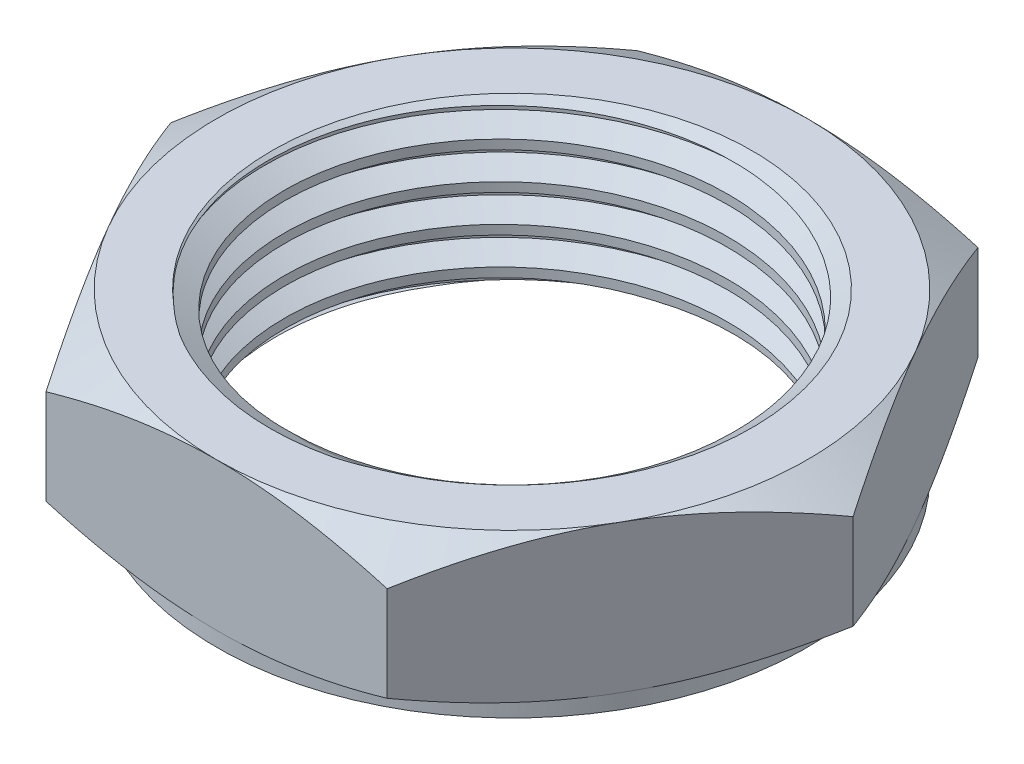
SolidWorks part; units mm, degrees
material "AISI Type 316L stainless steel"
ref_plane "Front Plane" through (0, 0, 0) normal (0, 0, 1) x (1, 0, 0)
ref_plane "Top Plane" through (0, 0, 0) normal (0, 1, 0) x (1, 0, 0)
ref_plane "Right Plane" through (0, 0, 0) normal (1, 0, 0) x (0, 0, -1)
sketch "Sketch1" plane through (0, 0, 0) normal (0, 1, 0) x (1, 0, 0)
  line L1 (18.4752, 0) -> (9.2376, 16)
  line L2 (9.2376, 16) -> (-9.2376, 16)
  line L3 (-9.2376, 16) -> (-18.4752, 0)
  line L4 (-18.4752, 0) -> (-9.2376, -16)
  line L5 (-9.2376, -16) -> (9.2376, -16)
  line L6 (9.2376, -16) -> (18.4752, 0)
  circle A0 centre (0, 0) radius 16 construction
  circle A1 centre (0, 0) radius 12
  dimension "D2" = 24
  dimension "D1" = 32
extrude "Boss-Extrude1" add sketch "Sketch1" along normal mid plane 8
sketch "Sketch2" plane through (0, 4, 0) normal (0, 1, 0) x (1, 0, 0)
  line L0 (-18.4752, 0) -> (-9.2376, -16) construction
  circle A0 centre (0, 0) radius 16
extrude "Cut-Extrude1" cut sketch "Sketch2" against normal through all draft 60 flip side to cut
mirror "Mirror1" about plane through (0, 0, 0) normal (0, 1, 0) of "Cut-Extrude1"
sketch "Sketch7" plane through (0, -4, 0) normal (0, -1, 0) x (1, 0, 0)
  line L0 (-9.2376, 16) -> (9.2376, 16) construction
  circle A0 centre (0, 0) radius 16
  circle A1 centre (0, 0) radius 12 construction
  circle A2 centre (0, 0) radius 12
extrude "Boss-Extrude2" add sketch "Sketch7" along normal blind 0.8
chamfer "Chamfer1" distance 1 angle 35 2 edges at (0, 4, 12) (0, -4.8, -12)
thread "M16*1.5" [suppressed] pitch 1.5 start angle 0, offset 3, length 0, pitch 1.5, diameter 16
ref_plane "Plane9" through (-8, 5.4748, 0) normal (0, 0, 1) x (-1, 0, 0)
sketch "Thread Profile9" plane through (-8, 5.4748, 0) normal (0, 0, 1) x (-1, 0, 0)
  line L0 (0, 0) -> (0, 1.5) construction
  line L11 (0, 0) -> (0, 1.3125)
  line L12 (0, 1.3125) -> (-0.8119, 0.8437)
  line L13 (-0.8119, 0.8437) -> (-0.8119, 0.4687)
  line L15 (-0.8119, 0.4687) -> (0, 0)
  line L17 (-0.8119, 0.6562) -> (0, 0.6562) construction
  point P2 (0, 0)
  dimension "Pitch" = 1.5
  dimension "Profile_Angle" = 60
  dimension "Profile_Land" = 0.375
  dimension "Profile_Height" = 0.8119
thread "M22*1.5" [suppressed] pitch 1.5 start angle 0, offset 8, length 0, pitch 1.5, diameter 22
ref_plane "Plane8" through (-11, 8.9748, 0) normal (0, 0, 1) x (-1, 0, 0)
sketch "Thread Profile8" plane through (-11, 8.9748, 0) normal (0, 0, 1) x (-1, 0, 0)
  line L0 (0, 0) -> (0, 1.5) construction
  line L11 (0, 0) -> (0, 1.3125)
  line L12 (0, 1.3125) -> (-0.8119, 0.8437)
  line L13 (-0.8119, 0.8437) -> (-0.8119, 0.4687)
  line L15 (-0.8119, 0.4687) -> (0, 0)
  line L17 (-0.8119, 0.6562) -> (0, 0.6562) construction
  point P2 (0, 0)
  dimension "Pitch" = 1.5
  dimension "Profile_Angle" = 60
  dimension "Profile_Land" = 0.375
  dimension "Profile_Height" = 0.8119
thread "M24*2" pitch 2 start angle 0, offset 3, length 0, pitch 2, diameter 24
ref_plane "Plane10" through (-12, 6.2998, 0) normal (0, 0, 1) x (-1, 0, 0)
sketch "Thread Profile10" plane through (-12, 6.2998, 0) normal (0, 0, 1) x (-1, 0, 0)
  line L0 (0, 0) -> (0, 2) construction
  line L1 (0, 0) -> (1.0825, 0.625)
  line L2 (1.0825, 0.625) -> (1.0825, 0.875)
  line L3 (1.0825, 0.875) -> (0, 1.5)
  line L4 (1.0825, 0.75) -> (0, 0.75) construction
  line L11 (0, 0) -> (0, 1.5)
  point P2 (0, 0)
  dimension "Pitch" = 2
  dimension "Profile_Angle" = 60
  dimension "Profile_Land" = 0.25
  dimension "Profile_Height" = 1.0825
equation "\"D\"= 24"
equation "\"Pitch\"= 2"
equation "\"AY\"= 32"
equation "\"AR\"= 8"
equation "\"D2@Sketch1\"=\"D\""
equation "\"D1@Sketch1\"=\"AY\""
equation "\"D1@Chamfer1\"=\"Pitch\"/2"
equation "\"D1@Boss-Extrude1\"=\"AR\""
equation "\"D3@M22*1.5\" = \"Pitch\" * 4"
equation "\"D2@M22*1.5\" = \"Pitch\" * 4"
